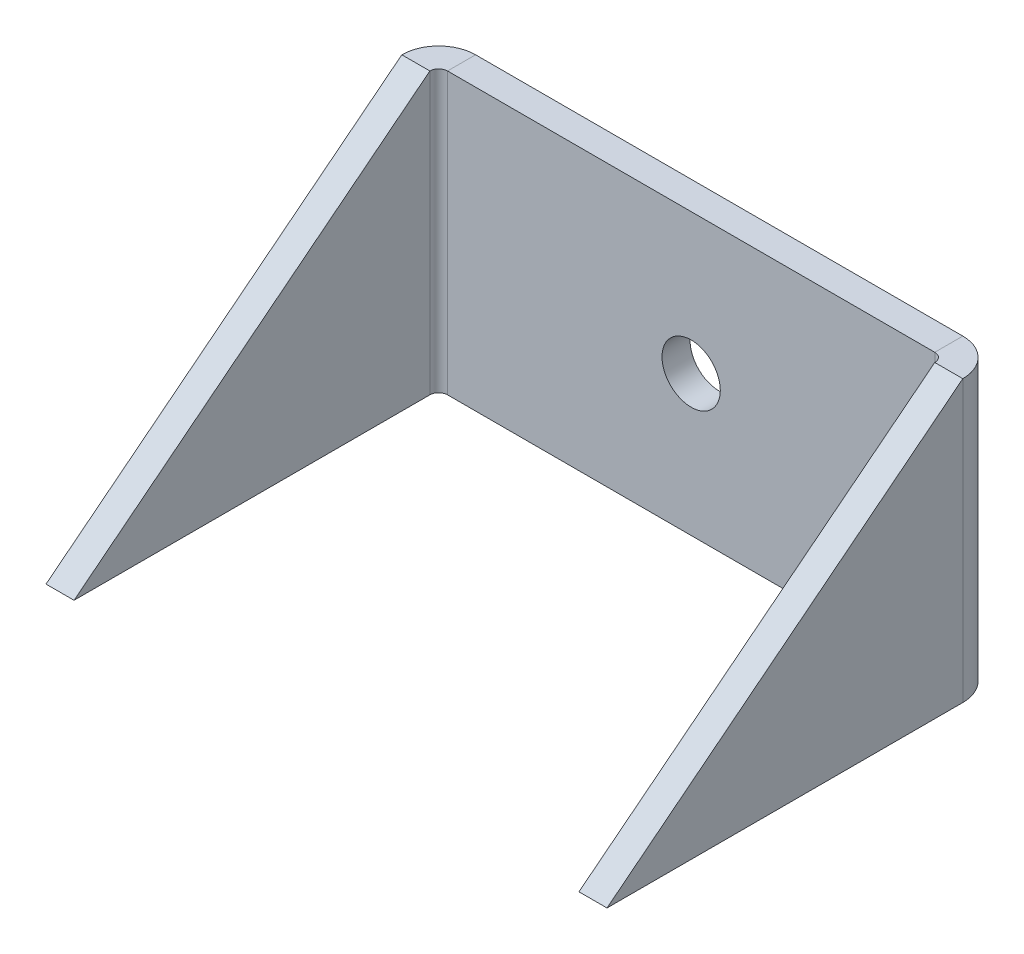
SolidWorks part; units mm, degrees
note: The reader was unsure of these and kept them because the rebuilt part matched: flange length of "Edge-Flange1".
material "6061-T6 (SS)"
ref_plane "X-Y Datum" through (0, 0, 0) normal (0, 0, 1) x (1, 0, 0)
ref_plane "X-Z Datum" through (0, 0, 0) normal (0, 1, 0) x (1, 0, 0)
ref_plane "Y-Z Datum" through (0, 0, 0) normal (1, 0, 0) x (0, 0, -1)
sketch "Sketch2" plane through (0, 0, 0) normal (0, 0, 1) x (1, 0, 0)
  line L1 (-28.575, 15.875) -> (28.575, 15.875)
  line L2 (-28.575, 15.875) -> (-28.575, -15.875)
  line L3 (-28.575, -15.875) -> (28.575, -15.875)
  line L4 (28.575, 15.875) -> (28.575, -15.875)
  line L5 (-28.575, 15.875) -> (28.575, -15.875) construction
  line L6 (-28.575, -15.875) -> (28.575, 15.875) construction
  circle A0 centre (0, 0) radius 3 construction
  point P0 (0, 0)
  dimension "D3" = 6
  dimension "D1" = 31.75
  dimension "D2" = 57.15
base flange "Base-Flange1" sketch "Sketch2" thickness 3.175 reverse thickness direction yes parameters "D1"=1
edge flange "Edge-Flange1" sketch "Sketch9" flange angle 90 flange length 44.45 flange position material outside bend radius 1 thickness 3.175 relief rectangular parameters "D6"=10
sketch "Sketch9" plane through (28.575, 0, 3.175) normal (1, 0, 0) x (0, 1, 0)
  line L2 (-15.875, 0) -> (-15.875, 41.275)
  line L3 (-15.875, 41.275) -> (15.875, 41.275)
  line L4 (15.875, 41.275) -> (15.875, 0)
  line L7 (-15.875, 0) -> (15.875, 0) construction
  line L8 (-15.875, 0) -> (15.875, 0)
bend "EdgeBend1" bend radius 1 bend angle 90 parameters "D5"=1
sketch "Sketch10" plane through (31.75, 0, 0) normal (1, 0, 0) x (0, 0, -1)
  line L0 (-4.175, 15.875) -> (-44.45, -15.875)
  line L1 (-44.45, 15.875) -> (-44.45, -15.875) construction
  line L3 (-44.45, -15.875) -> (-4.175, -15.875) construction
  line L7 (-4.175, -15.875) -> (-4.175, 15.875)
  line L8 (-4.175, 15.875) -> (-44.45, 15.875)
  line L9 (-44.45, 15.875) -> (-44.45, -15.875)
  line L10 (-44.45, -15.875) -> (-4.175, -15.875)
  line L12 (-4.175, 15.875) -> (-44.45, 15.875)
  line L13 (-44.45, 15.875) -> (-44.45, -15.875)
  dimension "D1" = 0
extrude "Cut-Extrude1" cut sketch "Sketch10" against normal blind 3.175 normal cut yes
mirror "Mirror1" about plane through (0, 0, 0) normal (1, 0, 0) of "Cut-Extrude1", "Edge-Flange1"
bend "MirrorBend1" bend radius 1 bend angle 90 parameters "D5"=2
sketch "Sketch11" [suppressed] plane through (32.75, 0, 0) normal (1, 0, 0) x (0, 0, -1)
  line L0 (-4.175, -15.875) -> (-44.45, 15.875)
extrude "Cut-Extrude2" [suppressed] cut sketch "Sketch11" against normal blind 3.175 and the other way through all
hole_wizard "M6 Clearance Hole1" positions "Sketch13" profile "Sketch14" hole size "M6" standard "ANSI Metric" end condition through all
sketch "Sketch13" plane through (0, 0, 3.175) normal (0, 0, 1) x (1, 0, 0)
  point P0 (0, 0)
sketch "Sketch14" plane through (0, 0, 3.175) normal (1, 0, 0) x (0, -1, 0)
  line L0 (0, 0) -> (0, 3.175)
  line L1 (0, 3.175) -> (3.3, 3.175)
  line L2 (3.3, 3.175) -> (3.3, 0)
  line L5 (3.3, 0) -> (0, 0)
  line L11 (0, -6.35) -> (0, 107.95) construction
  dimension "Thru Hole Dia." = 6.6
  dimension "Thru Hole Depth" = 3.175
sketch "Bend-Lines1" [suppressed] plane through (0, 0, 0) normal (0, 1, 0) x (1, 0, 0)
sketch "Bounding-Box1" [suppressed] plane through (0, 0, 0) normal (0, 1, 0) x (1, 0, 0)
sheet metal parameters "Sheet-Metal1" thickness 3.175 parameters "D1"=1
flat pattern "Flat-Pattern1" [suppressed]
sketch "Bend-Lines2" plane through (0, 0, 0) normal (0, 1, 0) x (1, 0, 0)
sketch3d "Bounding-Box2" [suppressed]
  line L0 (-63.5, -15.875, 0) -> (63.5, -15.875, 0) construction
  line L1 (-63.5, 15.875, 0) -> (63.5, 15.875, 0) construction
  line L2 (-63.5, -15.875, 0) -> (-63.5, 15.875, 0) construction
  line L3 (63.5, -15.875, 0) -> (63.5, 15.875, 0) construction
sheet metal parameters "Sheet-Metal2" thickness 3.175 parameters "D1"=1
flat pattern "Flat-Pattern1"
sketch "Bend-Lines2" plane through (0, 0, 0) normal (0, 0, -1) x (-1, 0, 0)
  line L0 (-30.6072, 15.875) -> (-30.6072, -15.875) construction
  line L1 (-30.6072, 15.875) -> (-30.6072, -15.875) construction
sketch3d "Bounding-Box2" [suppressed]
  line L0 (28.575, -15.875, 0) -> (-72.9144, -15.875, 0) construction
  line L1 (28.575, 15.875, 0) -> (-72.9144, 15.875, 0) construction
  line L2 (28.575, -15.875, 0) -> (28.575, 15.875, 0) construction
  line L3 (-72.9144, -15.875, 0) -> (-72.9144, 15.875, 0) construction
bend of the flat pattern "Flatten-<EdgeBend1>1"
sheet metal parameters "Sheet-Metal5" thickness 3.175 parameters "D1"=1
flat pattern "Flat-Pattern1"
sketch "Bend-Lines2" plane through (0, 0, 0) normal (0, 0, -1) x (-1, 0, 0)
  line L0 (-29.6072, 15.875) -> (-29.6072, -15.875) construction
  line L1 (-29.6072, 15.875) -> (-29.6072, -15.875) construction
  line L2 (29.6072, -15.875) -> (29.6072, 15.875) construction
  line L3 (29.6072, -15.875) -> (29.6072, 15.875) construction
sketch3d "Bounding-Box2" [suppressed]
  line L0 (71.9144, -15.875, 0) -> (-71.9144, -15.875, 0) construction
  line L1 (71.9144, 15.875, 0) -> (-71.9144, 15.875, 0) construction
  line L2 (71.9144, -15.875, 0) -> (71.9144, 15.875, 0) construction
  line L3 (-71.9144, -15.875, 0) -> (-71.9144, 15.875, 0) construction
bend of the flat pattern "Flatten-<EdgeBend1>1"
bend of the flat pattern "Flatten-<MirrorBend1>1"
sheet metal parameters "Sheet-Metal7" thickness 3.175 parameters "D1"=1
flat pattern "Flat-Pattern1"
sketch "Bend-Lines2" plane through (0, 0, 0) normal (0, 0, -1) x (-1, 0, 0)
  line L0 (-30.6072, 15.875) -> (-30.6072, -15.875) construction
  line L1 (-30.6072, 15.875) -> (-30.6072, -15.875) construction
sketch3d "Bounding-Box2" [suppressed]
  line L0 (28.575, -15.875, 0) -> (-72.9144, -15.875, 0) construction
  line L1 (28.575, 15.875, 0) -> (-72.9144, 15.875, 0) construction
  line L2 (28.575, -15.875, 0) -> (28.575, 15.875, 0) construction
  line L3 (-72.9144, -15.875, 0) -> (-72.9144, 15.875, 0) construction
bend of the flat pattern "Flatten-<EdgeBend1>1"
sheet metal parameters "Sheet-Metal8" thickness 3.175 parameters "D1"=1
flat pattern "Flat-Pattern1"
sketch "Bend-Lines2" plane through (0, 0, 0) normal (0, 0, -1) x (-1, 0, 0)
  line L0 (-30.6072, 15.875) -> (-30.6072, -15.875) construction
  line L1 (-30.6072, 15.875) -> (-30.6072, -15.875) construction
sketch3d "Bounding-Box2" [suppressed]
  line L0 (28.575, -15.875, 0) -> (-72.9144, -15.875, 0) construction
  line L1 (28.575, 15.875, 0) -> (-72.9144, 15.875, 0) construction
  line L2 (28.575, -15.875, 0) -> (28.575, 15.875, 0) construction
  line L3 (-72.9144, -15.875, 0) -> (-72.9144, 15.875, 0) construction
bend of the flat pattern "Flatten-<EdgeBend1>1"
sheet metal parameters "Sheet-Metal9" thickness 3.175 parameters "D1"=1
flat pattern "Flat-Pattern1"
sketch "Bend-Lines2" plane through (0, 0, 0) normal (0, 0, -1) x (-1, 0, 0)
  line L0 (-29.6072, 15.875) -> (-29.6072, -15.875) construction
  line L1 (-29.6072, 15.875) -> (-29.6072, -15.875) construction
  line L2 (29.6072, -15.875) -> (29.6072, 15.875) construction
  line L3 (29.6072, -15.875) -> (29.6072, 15.875) construction
sketch3d "Bounding-Box2" [suppressed]
  line L0 (71.9144, -15.875, 0) -> (-71.9144, -15.875, 0) construction
  line L1 (71.9144, 15.875, 0) -> (-71.9144, 15.875, 0) construction
  line L2 (71.9144, -15.875, 0) -> (71.9144, 15.875, 0) construction
  line L3 (-71.9144, -15.875, 0) -> (-71.9144, 15.875, 0) construction
bend of the flat pattern "Flatten-<EdgeBend1>1"
bend of the flat pattern "Flatten-<MirrorBend1>1"
